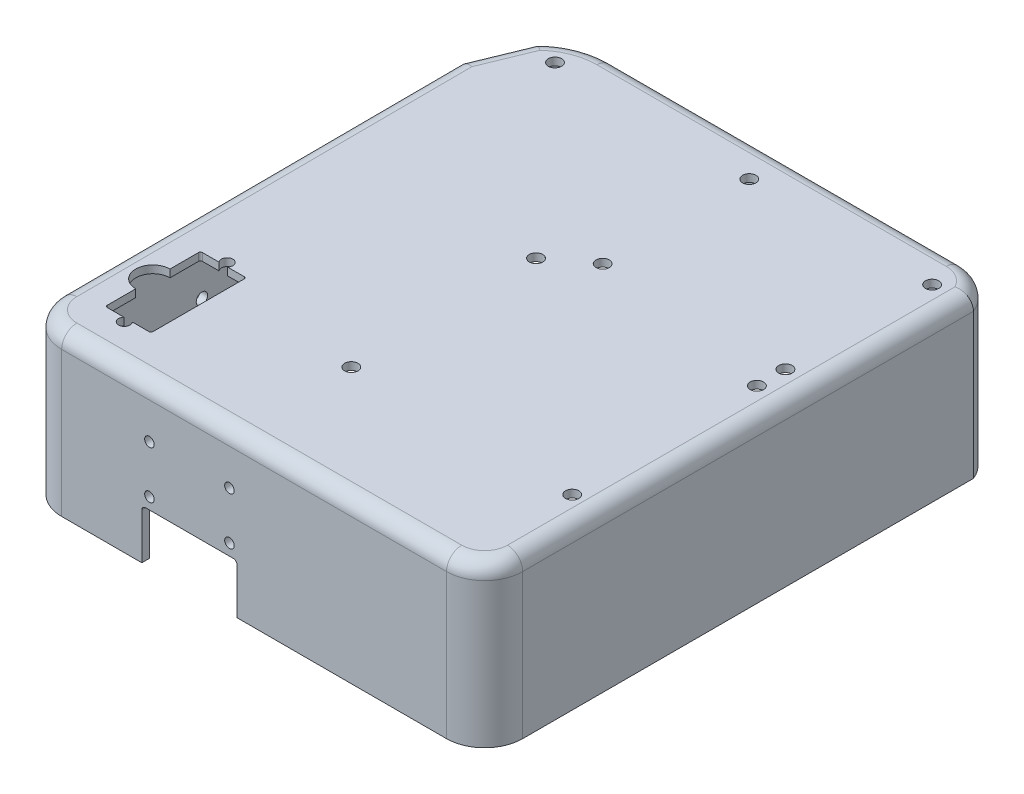
SolidWorks part; units mm, degrees
ref_plane "Front Plane" through (0, 0, 0) normal (0, 0, 1) x (1, 0, 0)
ref_plane "Top Plane" through (0, 0, 0) normal (0, 1, 0) x (1, 0, 0)
ref_plane "Right Plane" through (0, 0, 0) normal (1, 0, 0) x (0, 0, -1)
sketch "Sketch1" plane through (0, 0, 0) normal (0, 1, 0) x (1, 0, 0)
  line L0 (88.5234, -42.2941) -> (88.5234, 38.2257) construction
  line L1 (87.7677, 42.1498) -> (61.5953, 107.5809) construction
  line L2 (51.785, 114.2228) -> (-39.8883, 114.2228)
  line L3 (-59.9447, 107.5809) -> (-86.1171, 42.1498) construction
  line L4 (-86.8728, 38.2257) -> (-86.8728, -42.2941) construction
  line L5 (-85.2668, -47.8941) -> (-50.3539, -103.7546) construction
  line L6 (-41.394, -108.7207) -> (43.0446, -108.7207) construction
  line L7 (52.0046, -103.7546) -> (86.9174, -47.8941) construction
  line L8 (61.5953, 107.5809) -> (61.5953, -10.7772)
  line L9 (51.5953, -20.7772) -> (-49.4467, -20.7772)
  line L10 (-59.4466, -10.8193) -> (-59.8881, 94.1386)
  line L11 (-54.0601, 108.3351) -> (-59.8881, 94.1386)
  arc A0 (88.5234, 38.2257) -> (87.7677, 42.1498) centre (77.9574, 38.2257) ccw construction
  arc A1 (61.5953, 107.5809) -> (51.785, 114.2228) centre (51.785, 103.6567) ccw
  arc A2 (-50.1343, 114.2228) -> (-59.9447, 107.5809) centre (-50.1343, 103.6567) ccw construction
  arc A3 (-86.1171, 42.1498) -> (-86.8728, 38.2257) centre (-76.3068, 38.2257) ccw construction
  arc A4 (-86.8728, -42.2941) -> (-85.2668, -47.8941) centre (-76.3068, -42.2941) ccw construction
  arc A5 (-50.3539, -103.7546) -> (-41.394, -108.7207) centre (-41.394, -98.1546) ccw construction
  arc A6 (43.0446, -108.7207) -> (52.0046, -103.7546) centre (43.0446, -98.1546) ccw construction
  arc A7 (86.9174, -47.8941) -> (88.5234, -42.2941) centre (77.9574, -42.2941) ccw construction
  arc A8 (61.5953, -10.7772) -> (51.5953, -20.7772) centre (51.5953, -10.7772) cw
  arc A9 (-49.4467, -20.7772) -> (-59.4466, -10.8193) centre (-49.4467, -10.7772) cw
  arc A10 (-39.8883, 114.2228) -> (-54.0601, 108.3351) centre (-39.8883, 94.2228) ccw
  point P31 (61.5953, -20.7772)
  point P34 (-59.4047, -20.7772)
  dimension "D3" = 10
  dimension "D4" = 20
  dimension "D1" = 135
  dimension "D2" = 121
extrude "Boss-Extrude1" add sketch "Sketch1" along normal blind 2
sketch "Sketch2" plane through (0, 0, 0) normal (0, -1, 0) x (1, 0, 0)
  line L4 (61.5953, -107.5809) -> (61.5953, 10.7772)
  line L5 (51.5953, 20.7772) -> (-49.4467, 20.7772)
  line L6 (-59.4466, 10.8193) -> (-59.8881, -94.1386)
  line L7 (-39.8883, -114.2228) -> (51.785, -114.2228)
  line L8 (61.5953, -107.5809) -> (61.5953, 10.7772)
  line L9 (51.5953, 20.7772) -> (-49.4467, 20.7772)
  line L10 (-59.4466, 10.8193) -> (-59.8881, -94.1386)
  line L11 (-39.8883, -114.2228) -> (51.785, -114.2228)
  line L13 (59.5953, -107.1747) -> (59.5953, 10.7772)
  line L14 (51.5953, 18.7772) -> (-49.4467, 18.7772)
  line L15 (-57.4466, 10.8109) -> (-57.8865, -93.7481)
  line L16 (-57.8865, -93.7481) -> (-52.3656, -107.1964)
  line L17 (-59.8881, -94.1386) -> (-54.0601, -108.3351)
  line L18 (-59.8881, -94.1386) -> (-54.0601, -108.3351)
  line L19 (-39.8883, -112.2228) -> (51.785, -112.2228)
  arc A4 (51.785, -114.2228) -> (61.5953, -107.5809) centre (51.785, -103.6567) ccw
  arc A5 (61.5953, 10.7772) -> (51.5953, 20.7772) centre (51.5953, 10.7772) ccw
  arc A6 (-49.4467, 20.7772) -> (-59.4466, 10.8193) centre (-49.4467, 10.7772) ccw
  arc A7 (-54.0601, -108.3351) -> (-39.8883, -114.2228) centre (-39.8883, -94.2228) ccw
  arc A8 (51.785, -114.2228) -> (61.5953, -107.5809) centre (51.785, -103.6567) ccw
  arc A9 (61.5953, 10.7772) -> (51.5953, 20.7772) centre (51.5953, 10.7772) ccw
  arc A10 (-49.4467, 20.7772) -> (-59.4466, 10.8193) centre (-49.4467, 10.7772) ccw
  arc A12 (51.785, -112.2228) -> (59.5953, -107.1747) centre (51.785, -103.6567) ccw
  arc A13 (59.5953, 10.7772) -> (51.5953, 18.7772) centre (51.5953, 10.7772) ccw
  arc A14 (-49.4467, 18.7772) -> (-57.4466, 10.8109) centre (-49.4467, 10.7772) ccw
  arc A15 (-52.3656, -107.1964) -> (-39.8883, -112.2228) centre (-39.8883, -94.2228) ccw
  arc A17 (-54.0601, -108.3351) -> (-39.8883, -114.2228) centre (-39.8883, -94.2228) ccw
  point P21 (-57.888, -94.1105)
  point P22 (-39.1495, -93.4871)
  point P23 (-39.8518, -112.2228)
  dimension "D1" = 0
  dimension "D2" = 2
extrude "Boss-Extrude2" add sketch "Sketch2" along normal blind 40
sketch "Sketch3" plane through (0, 0, 20.7772) normal (0, 0, 1) x (1, 0, 0)
  line L0 (51.5953, -40) -> (-49.4467, -40) construction
  line L1 (-28.4047, -27) -> (-3.4047, -27)
  line L2 (-28.4047, -27) -> (-28.4047, -40)
  line L3 (-28.4047, -40) -> (-3.4047, -40)
  line L4 (-3.4047, -27) -> (-3.4047, -40)
  line L5 (-28.4047, -27) -> (-3.4047, -40) construction
  line L6 (-28.4047, -40) -> (-3.4047, -27) construction
  line L7 (61.5953, 2) -> (61.5953, -40) construction
  circle A0 centre (-5.4047, -24) radius 1.25
  circle A1 centre (-26.4047, -24) radius 1.25
  circle A2 centre (-5.4047, -11.5) radius 1.25
  circle A3 centre (-26.4047, -11.5) radius 1.25
  point P0 (-15.9047, -33.5)
  dimension "D7" = 2.5
  dimension "D8" = 2.5
  dimension "D9" = 2.5
  dimension "D10" = 2.5
  dimension "D1" = 65
  dimension "D2" = 25
  dimension "D3" = 13
  dimension "D4" = 21
  dimension "D5" = 21
  dimension "D6" = 12.5
  dimension "D11" = 16
  dimension "D12" = 2
extrude "Cut-Extrude1" cut sketch "Sketch3" against normal blind 2
fillet "Fillet1" radius 1 2 edges at (-3.4047, -27, 19.7772) (-28.4047, -27, 19.7772)
fillet "Fillet2" radius 4 9 edges at (61.5953, 2, -48.4018) (58.6664, 2, 17.8483) (1.0743, 2, 20.7772) (-56.5029, 2, 17.8631) (-59.6674, 2, -41.6597) (5.9483, 2, -114.2228) (57.7086, 2, -112.4061) (-47.5614, 2, -112.6923) (-56.9741, 2, -101.2369)
sketch "Sketch5" plane through (0, 2, 0) normal (0, 1, 0) x (1, 0, 0)
  line L0 (-55.8848, 93.3576) -> (-55.4466, -10.8025) construction
  line L1 (-49.0055, -9.2772) -> (-38.0055, -9.2772)
  line L2 (-49.5055, -8.7772) -> (-49.5055, 15.2228)
  line L3 (-49.0055, 15.7228) -> (-38.0055, 15.7228)
  line L4 (-37.5055, -8.7772) -> (-37.5055, 15.2228)
  line L5 (-49.5055, -9.2772) -> (-37.5055, 15.7228) construction
  line L6 (-49.5055, 15.7228) -> (-37.5055, -9.2772) construction
  line L7 (-49.4467, -16.7772) -> (51.5953, -16.7772) construction
  circle A0 centre (-43.5055, 16.7228) radius 1.5
  circle A1 centre (-43.5055, -10.2772) radius 1.5
  arc A2 (-38.0055, 15.7228) -> (-37.5055, 15.2228) centre (-38.0055, 15.2228) cw
  arc A3 (-38.0055, -9.2772) -> (-37.5055, -8.7772) centre (-38.0055, -8.7772) ccw
  arc A4 (-49.0055, -9.2772) -> (-49.5055, -8.7772) centre (-49.0055, -8.7772) cw
  arc A5 (-49.5055, 15.2228) -> (-49.0055, 15.7228) centre (-49.0055, 15.2228) cw
  point P0 (-43.5055, 3.2228)
  dimension "D5" = 3
  dimension "D6" = 3
  dimension "D7" = 0.5
  dimension "D1" = 25
  dimension "D2" = 12
  dimension "D3" = 27
  dimension "D4" = 1
  dimension "D8" = 6
  dimension "D9" = 6
  dimension "D10" = 12
  dimension "D11" = 20
extrude "Cut-Extrude2" cut sketch "Sketch5" against normal blind 2 contours A5 L2 A4 L1 A1 A3 L4 A2 L3 A0 | L1 A1 | L1 A1 | L3 A0 | L3 A0 region at (-43.5055, 2, -3.2228) region at (-43.5055, 2, 9.0741) region at (-43.5055, 2, 10.4252) region at (-43.5055, 2, -16.8708) region at (-43.5055, 2, -15.5196)
sketch "Sketch6" plane through (-59.4911, 0, 0.2503) normal (-1, 0, 0.0042) x (0.0042, 0, 1)
  line L0 (10.5691, -2) -> (10.5691, -40) construction
  line L1 (10.5691, -2) -> (-94.3897, -2) construction
  line L2 (10.5691, -40) -> (-94.3897, -40) construction
  line L3 (-28.9309, -36.5) -> (-19.9309, -36.5)
  line L4 (-29.4309, -36) -> (-29.4309, -34)
  line L5 (-28.9309, -33.5) -> (-19.9309, -33.5)
  line L6 (-19.4309, -36) -> (-19.4309, -34)
  line L7 (-29.4309, -36.5) -> (-19.4309, -33.5) construction
  line L8 (-29.4309, -33.5) -> (-19.4309, -36.5) construction
  line L9 (-49.4309, -36) -> (-49.4309, -34)
  line L10 (-48.9309, -36.5) -> (-39.9309, -36.5)
  line L11 (-39.4309, -36) -> (-39.4309, -34)
  line L12 (-48.9309, -33.5) -> (-39.9309, -33.5)
  line L13 (-69.4309, -36) -> (-69.4309, -34)
  line L14 (-68.9309, -36.5) -> (-59.9309, -36.5)
  line L15 (-59.4309, -36) -> (-59.4309, -34)
  line L16 (-68.9309, -33.5) -> (-59.9309, -33.5)
  line L17 (-89.4309, -36) -> (-89.4309, -34)
  line L18 (-88.9309, -36.5) -> (-79.9309, -36.5)
  line L19 (-79.4309, -36) -> (-79.4309, -34)
  line L20 (-88.9309, -33.5) -> (-79.9309, -33.5)
  circle A0 centre (-24.4309, -17) radius 1.5
  arc A1 (-19.9309, -33.5) -> (-19.4309, -34) centre (-19.9309, -34) cw
  arc A2 (-19.9309, -36.5) -> (-19.4309, -36) centre (-19.9309, -36) ccw
  arc A3 (-28.9309, -36.5) -> (-29.4309, -36) centre (-28.9309, -36) cw
  arc A4 (-29.4309, -34) -> (-28.9309, -33.5) centre (-28.9309, -34) cw
  circle A5 centre (-44.4309, -17) radius 1.5
  arc A6 (-49.4309, -34) -> (-48.9309, -33.5) centre (-48.9309, -34) cw
  arc A7 (-48.9309, -36.5) -> (-49.4309, -36) centre (-48.9309, -36) cw
  arc A8 (-39.9309, -36.5) -> (-39.4309, -36) centre (-39.9309, -36) ccw
  arc A9 (-39.9309, -33.5) -> (-39.4309, -34) centre (-39.9309, -34) cw
  circle A10 centre (-64.4309, -17) radius 1.5
  arc A11 (-69.4309, -34) -> (-68.9309, -33.5) centre (-68.9309, -34) cw
  arc A12 (-68.9309, -36.5) -> (-69.4309, -36) centre (-68.9309, -36) cw
  arc A13 (-59.9309, -36.5) -> (-59.4309, -36) centre (-59.9309, -36) ccw
  arc A14 (-59.9309, -33.5) -> (-59.4309, -34) centre (-59.9309, -34) cw
  circle A15 centre (-84.4309, -17) radius 1.5
  arc A16 (-89.4309, -34) -> (-88.9309, -33.5) centre (-88.9309, -34) cw
  arc A17 (-88.9309, -36.5) -> (-89.4309, -36) centre (-88.9309, -36) cw
  arc A18 (-79.9309, -36.5) -> (-79.4309, -36) centre (-79.9309, -36) ccw
  arc A19 (-79.9309, -33.5) -> (-79.4309, -34) centre (-79.9309, -34) cw
  point P6 (-24.4309, -35)
  dimension "D2" = 3
  dimension "D8" = 0.5
  dimension "D1" = 35
  dimension "D3" = 15
  dimension "D4" = 3
  dimension "D5" = 10
  dimension "D6" = 5
  dimension "D7" = 5
  dimension "D9" = 4
extrude "Cut-Extrude3" cut sketch "Sketch6" against normal blind 2
sketch "Sketch7" plane through (0, 2, 0) normal (0, 1, 0) x (1, 0, 0)
  line L0 (51.5953, -20.7772) -> (-49.4467, -20.7772) construction
  line L1 (57.5953, -10.7772) -> (57.5953, 106.715) construction
  circle A0 centre (54.5953, 9.2228) radius 1.75
  circle A1 centre (-3.4047, 9.2228) radius 1.75
  circle A2 centre (-3.9047, 58.2202) radius 1.75
  circle A3 centre (54.0953, 58.2202) radius 1.75
  circle A5 centre (54.0953, 104.2202) radius 1.75
  circle A6 centre (54.0953, 65.7202) radius 1.75
  circle A7 centre (6.0953, 65.7202) radius 1.75
  circle A8 centre (6.0953, 104.2202) radius 1.75
  dimension "D1" = 3.5
  dimension "D2" = 3.5
  dimension "D6" = 3.5
  dimension "D7" = 3.5
  dimension "D16" = 3.5
  dimension "D17" = 3.5
  dimension "D18" = 3.5
  dimension "D19" = 3.5
  dimension "D3" = 58
  dimension "D4" = 30
  dimension "D5" = 3
  dimension "D8" = 49
  dimension "D9" = 49
  dimension "D10" = 3.5
  dimension "D11" = 58
  dimension "D12" = 46
  dimension "D13" = 38.5
  dimension "D14" = 3.5
  dimension "D15" = 3.5
  dimension "D20" = 48
  dimension "D21" = 48
  dimension "D22" = 38.5
extrude "Cut-Extrude4" cut sketch "Sketch7" against normal blind 2
sketch "Sketch8" plane through (0, -40, 0) normal (0, -1, 0) x (1, 0, 0)
  line L0 (-39.8883, -112.2228) -> (51.785, -112.2228) construction
  circle A0 centre (-53.4466, 14.7772) radius 1
  circle A1 centre (55.5953, 14.7772) radius 1
  circle A2 centre (55.785, -109.1747) radius 1
  circle A3 centre (-46.3656, -109.2228) radius 1
  arc A4 (59.5953, -107.1747) -> (51.785, -112.2228) centre (51.785, -103.6567) cw
  arc A5 (-57.4466, 10.8109) -> (-49.4467, 18.7772) centre (-49.4467, 10.7772) cw
  arc A6 (-57.4466, 10.8109) -> (-49.4467, 18.7772) centre (-57.4466, 18.8109) ccw
  arc A7 (51.5953, 18.7772) -> (59.5953, 10.7772) centre (51.5953, 10.7772) cw
  arc A8 (59.5953, 10.7772) -> (51.5953, 18.7772) centre (51.5953, 10.7772) ccw construction
  arc A9 (59.5953, 10.7772) -> (51.5953, 18.7772) centre (51.5953, 10.7772) ccw construction
  arc A10 (51.5953, 18.7772) -> (59.5953, 10.7772) centre (59.8952, 19.0771) ccw
  arc A11 (51.785, -112.2228) -> (59.5953, -107.1747) centre (51.785, -103.6567) ccw construction
  arc A12 (51.785, -112.2228) -> (59.5953, -107.1747) centre (51.785, -103.6567) ccw construction
  arc A13 (51.785, -112.2228) -> (59.5953, -107.1747) centre (57.7485, -112.8834) cw
  arc A14 (-52.3656, -107.1964) -> (-39.8883, -112.2228) centre (-48.8921, -116.5738) cw
  arc A15 (-52.3656, -107.1964) -> (-39.8883, -112.2228) centre (-39.8883, -94.2228) ccw construction
  arc A16 (-52.3656, -107.1964) -> (-39.8883, -112.2228) centre (-39.8883, -94.2228) ccw
  dimension "D1" = 2
  dimension "D2" = 2
  dimension "D3" = 2
  dimension "D4" = 2
  dimension "D7" = 8
  dimension "D8" = 8
  dimension "D9" = 8
  dimension "D10" = 8.3053
  dimension "D15" = 8.566
  dimension "D16" = 6
  dimension "D19" = 10
  dimension "D20" = 18
  dimension "D5" = 4
  dimension "D6" = 4
  dimension "D11" = 4
  dimension "D12" = 4
  dimension "D13" = 4
  dimension "D14" = 2
  dimension "D17" = 3
  dimension "D18" = 6
extrude "Boss-Extrude3" add sketch "Sketch8" against normal blind 5 contours A3 | A2 | A1 | A0 | A6 A5 | A10 A7 | A13 A4 | A16 A14 region at (-53.4466, -40, 14.7772) region at (55.5953, -40, 14.7772) region at (55.785, -40, -109.1747) region at (-46.3656, -40, -109.2228)
sketch "Sketch10" plane through (0, 2, 0) normal (0, 1, 0) x (1, 0, 0)
  line L0 (-49.5055, -8.7772) -> (-49.5055, 15.2228) construction
  line L1 (-49.0055, 15.7228) -> (-44.6236, 15.7228) construction
  line L2 (-49.0055, -9.2772) -> (-44.6236, -9.2772) construction
  line L3 (-49.5055, -1.2772) -> (-49.5055, 7.7228)
  arc A0 (-49.5055, -1.2772) -> (-49.5055, 7.7228) centre (-49.5055, 3.2228) cw
  dimension "D1" = 4.5
  dimension "D2" = 8
  dimension "D3" = 8
extrude "Cut-Extrude5" cut sketch "Sketch10" against normal blind 2
sketch "Sketch11" plane through (0, 2, 0) normal (0, 1, 0) x (1, 0, 0)
  line L0 (51.785, 110.2228) -> (-39.8883, 110.2228) construction
  line L1 (-55.8848, 93.3576) -> (-55.4466, -10.8025) construction
  circle A0 centre (-45.9346, 105.2228) radius 1.75
  dimension "D1" = 3.5
  dimension "D2" = 5
  dimension "D3" = 10
extrude "Cut-Extrude6" cut sketch "Sketch11" against normal blind 10
